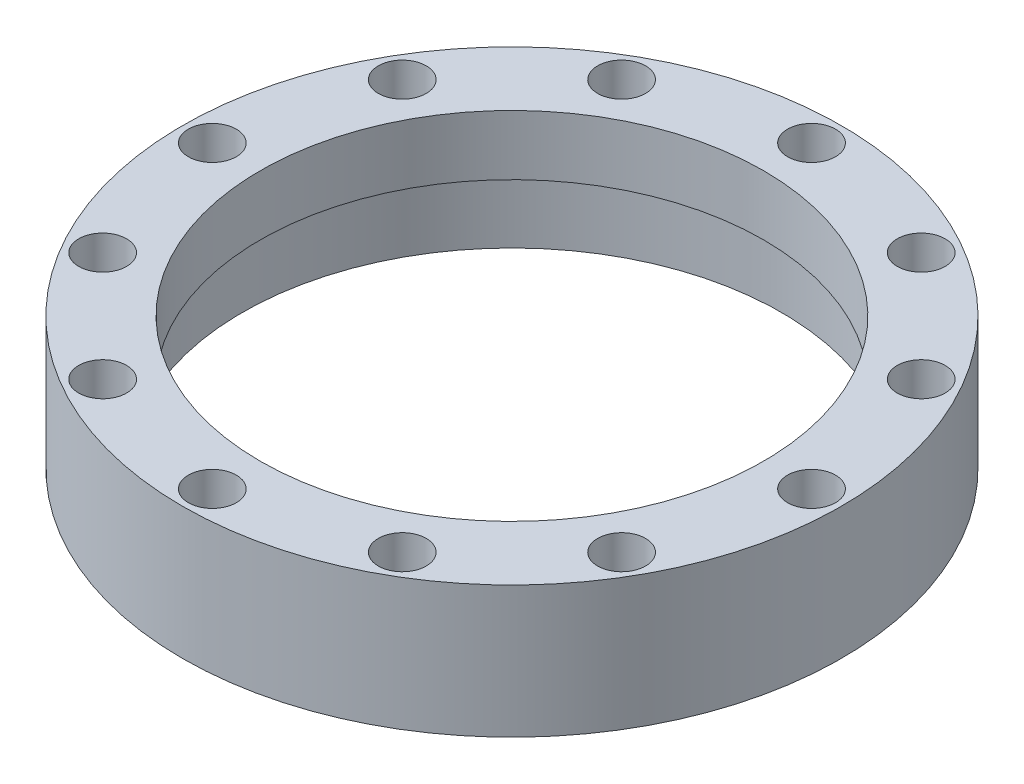
SolidWorks part; units mm, degrees
ref_plane "Front Plane" through (0, 0, 0) normal (0, 0, 1) x (1, 0, 0)
ref_plane "Top Plane" through (0, 0, 0) normal (0, 1, 0) x (1, 0, 0)
ref_plane "Right Plane" through (0, 0, 0) normal (1, 0, 0) x (0, 0, -1)
sketch "Sketch1" plane through (0, 0, 0) normal (0, 1, 0) x (1, 0, 0)
  line L0 (0, 48.2621) -> (0, -49.945) construction
  circle A0 centre (0, 0) radius 27.5
  circle A1 centre (0, 0) radius 25 construction
  circle A2 centre (0, 0) radius 22.5
  circle A3 centre (0, 25) radius 1.5
  circle A4 centre (12.5, 21.6506) radius 1.5
  circle A5 centre (21.6506, 12.5) radius 1.5
  circle A6 centre (25, 0) radius 1.5
  circle A7 centre (21.6506, -12.5) radius 1.5
  circle A8 centre (12.5, -21.6506) radius 1.5
  circle A9 centre (0, -25) radius 1.5
  circle A10 centre (-12.5, -21.6506) radius 1.5
  circle A11 centre (-21.6506, -12.5) radius 1.5
  circle A12 centre (-25, 0) radius 1.5
  circle A13 centre (-21.6506, 12.5) radius 1.5
  circle A14 centre (-12.5, 21.6506) radius 1.5
  point P31 (0, 0)
  dimension "D1" = 55
  dimension "D2" = 50
  dimension "D3" = 45
  dimension "D4" = 3
  dimension "D5" = 12
extrude "Boss-Extrude1" add sketch "Sketch1" along normal blind 11
sketch "Sketch2" plane through (0, 11, 0) normal (0, 1, 0) x (1, 0, 0)
  circle A0 centre (0, 0) radius 22.5
  circle A1 centre (0, 0) radius 21
  dimension "D1" = 42
extrude "Boss-Extrude2" add sketch "Sketch2" against normal blind 5
sketch "Sketch3" plane through (0, 11, 0) normal (0, 1, 0) x (1, 0, 0)
  circle A0 centre (0, 25) radius 2
  circle A1 centre (12.5, 21.6506) radius 2
  circle A2 centre (21.6506, 12.5) radius 2
  circle A3 centre (25, 0) radius 2
  circle A4 centre (21.6506, -12.5) radius 2
  circle A5 centre (12.5, -21.6506) radius 2
  circle A6 centre (0, -25) radius 2
  circle A7 centre (-12.5, -21.6506) radius 2
  circle A8 centre (-21.6506, -12.5) radius 2
  circle A9 centre (-25, 0) radius 2
  circle A10 centre (-21.6506, 12.5) radius 2
  circle A11 centre (-12.5, 21.6506) radius 2
  point P28 (0, 0)
  dimension "D1" = 4
  dimension "D2" = 12
extrude "Cut-Extrude1" cut sketch "Sketch3" against normal blind 5
